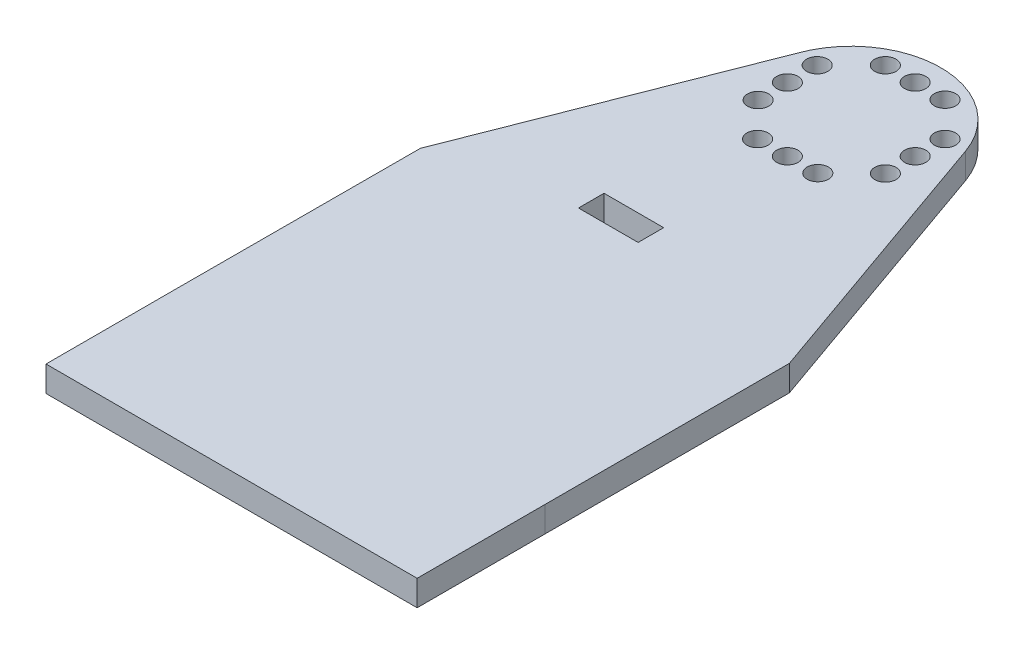
SolidWorks part; units mm, degrees
ref_plane "Front Plane" through (0, 0, 0) normal (0, 0, 1) x (1, 0, 0)
ref_plane "Top Plane" through (0, 0, 0) normal (0, 1, 0) x (1, 0, 0)
ref_plane "Right Plane" through (0, 0, 0) normal (1, 0, 0) x (0, 0, -1)
sketch "Sketch2" plane through (0, 0, 0) normal (0, 1, 0) x (1, 0, 0)
  line L0 (-0.0001, 7.5128) -> (3.4999, 7.5129) construction
  line L1 (0, 0) -> (0, -57.0944) construction
  line L3 (0, 0) -> (7.5, 0.013) construction
  line L5 (0, 0) -> (0.0001, -7.4872) construction
  line L6 (21.1625, -28.4147) -> (9.9242, 3.5128)
  line L7 (-22.3399, -28.2122) -> (-9.9242, 3.5128)
  line L9 (0, 0) -> (0.0001, -7.4872) construction
  line L11 (7.5001, -3.487) -> (7.5001, 3.513) construction
  line L13 (-7.5, 3.5127) -> (-7.5, 0.0127) construction
  line L22 (-22.3884, -57.0944) -> (21.1625, -57.0944)
  line L23 (-22.3884, -57.0944) -> (21.1625, -57.0944) construction
  line L25 (-22.3884, -57.0944) -> (-22.3399, -28.2122)
  line L26 (21.1625, -28.4147) -> (21.1625, -57.0944)
  line L27 (21.1625, -28.4147) -> (-22.3399, -28.2122)
  circle A0 centre (0, 0) radius 10.5276
  circle A1 centre (0.0001, -7.4872) radius 1.25
  circle A2 centre (-7.5, 0.0127) radius 1.25
  circle A3 centre (-0.0001, 7.5128) radius 1.25
  circle A4 centre (7.5, 0.013) radius 1.25
  circle A5 centre (-7.4282, -3.4865) radius 1.25
  circle A6 centre (-7.5, 3.5127) radius 1.25
  circle A7 centre (-3.5001, 7.5128) radius 1.25
  circle A8 centre (3.4999, 7.5129) radius 1.25
  circle A9 centre (7.5001, 3.513) radius 1.25
  circle A10 centre (7.5001, -3.487) radius 1.25
  circle A11 centre (-3.4999, -7.4872) radius 1.25
  circle A12 centre (3.4994, -7.4154) radius 1.25
extrude "Boss-Extrude1" add sketch "Sketch2" against normal blind 3 contours L26 L27 L25 L22 | A0 L27 | A0 A12 A11 A10 A9 A8 A7 A6 A5 A4 A3 A1 region at (-0.0012, 0, 0.0038) region at (-0.4242, 0, 18.1835) region at (-0.6264, 0, 42.7065)
sketch "Sketch6" plane through (0, -3, 0) normal (0, -1, 0) x (1, 0, 0)
  line L0 (-22.3884, 57.0944) -> (-6.5, 57.0944) construction
  line L1 (-22.3884, 57.0944) -> (21.1625, 57.0944) construction
  line L2 (-22.3884, 57.0944) -> (-6.5, 57.0944) construction
  line L3 (-6.5, 57.0944) -> (-3.5, 57.0944) construction
  line L4 (-3.5, 57.0944) -> (-3.5, 27.9644) construction
  line L5 (-3.5, 27.9644) -> (-6.5, 27.9644) construction
  line L6 (-6.5, 27.9644) -> (-6.5, 57.0944) construction
  line L7 (-6.5, 57.0944) -> (-6.5, 27.9644)
  line L8 (-6.5, 27.9644) -> (-3.5, 27.9644)
  line L9 (-3.5, 27.9644) -> (-3.5, 57.0944)
  line L10 (-3.5, 57.0944) -> (-6.5, 57.0944)
  line L17 (-3.5, 27.9644) -> (-6.5, 27.9644) construction
  line L19 (-6.5, 27.9644) -> (-3.5, 27.9644) construction
extrude "Boss-Extrude3" add sketch "Sketch6" against normal blind 11.68
sketch "Sketch9" plane through (-3.5, 0, 0) normal (1, 0, 0) x (0, 0, -1)
  line L0 (-37.3694, 3.88) -> (-37.3694, 0) construction
  line L1 (-57.0944, 0) -> (-27.9644, 0) construction
  line L4 (-37.3694, 3.88) -> (-47.7194, 3.88) construction
  circle A0 centre (-37.3694, 3.88) radius 1.75
  circle A1 centre (-47.7194, 3.88) radius 1.75
extrude "Cut-Extrude2" cut sketch "Sketch9" against normal blind 5
mirror "Mirror1" about plane through (0, 8.68, 0) normal (0, -1, 0) of bodies 109
delete or keep bodies "Body-Delete/Keep 1" type delete bodies bodies 109
sketch "Sketch10" plane through (0, 0, 57.0944) normal (0, 0, 1) x (1, 0, 0)
  line L1 (-22.3884, 17.36) -> (21.1625, 17.36)
  line L2 (-22.3884, 17.36) -> (-22.3884, 20.36)
  line L3 (-22.3884, 20.36) -> (21.1625, 20.36)
  line L4 (21.1625, 17.36) -> (21.1625, 20.36)
extrude "Boss-Extrude4" add sketch "Sketch10" along normal blind 15
sketch "Sketch11" plane through (0, 17.36, 0) normal (0, -1, 0) x (1, 0, 0)
  line L0 (0, 0) -> (0, 25) construction
  line L1 (0, 25) -> (-7, 25)
  line L2 (-7, 25) -> (1, 25)
  line L3 (1, 25) -> (1, 22)
  line L4 (1, 22) -> (-7, 22)
  line L5 (-7, 22) -> (-7, 25)
extrude "Cut-Extrude3" cut sketch "Sketch11" against normal blind 10 contours L4 L0 L1 L5 region at (-3.5, 17.36, 23.5)
